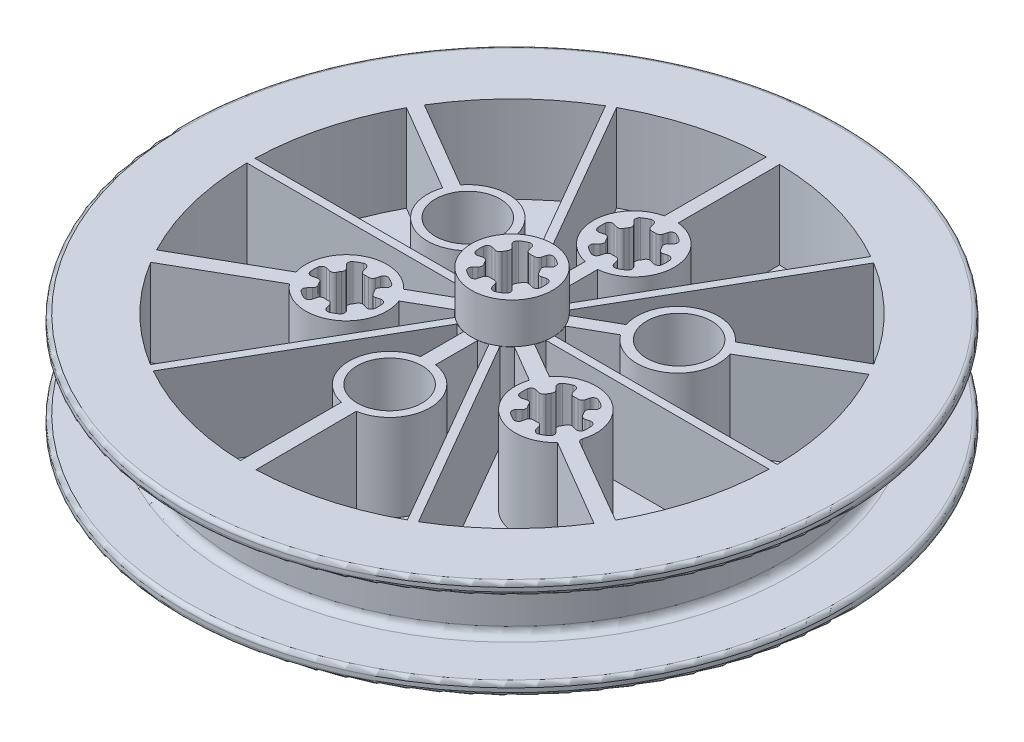
SolidWorks part; units mm, degrees
note: The reader was unsure of these and kept them because the rebuilt part matched: shared geometry of "Sketch1<25>", "Sketch1<26>", "Sketch1<27>".
ref_plane "Front Plane" through (0, 0, 0) normal (0, 0, 1) x (1, 0, 0)
ref_plane "Top Plane" through (0, 0, 0) normal (0, 1, 0) x (1, 0, 0)
ref_plane "Right Plane" through (0, 0, 0) normal (1, 0, 0) x (0, 0, -1)
sketch "Sketch1" plane through (0, 0, 0) normal (0, 1, 0) x (1, 0, 0)
  line L0 (-1.0649, -4.9092) -> (-1.0649, -10.2318)
  line L1 (-0.5943, 17.4024) -> (-0.9826, 18.8513)
  line L2 (0.6997, 17.4024) -> (1.088, 18.8513)
  line L3 (2.4675, 15.6346) -> (3.9164, 16.0228)
  line L4 (-2.3621, 15.6346) -> (-3.811, 16.0228)
  line L5 (-2.3621, 14.3405) -> (-3.811, 13.9523)
  line L6 (0.6997, 12.5728) -> (1.088, 11.1239)
  line L7 (1.8205, 13.2198) -> (2.8811, 12.1591)
  line L8 (14.721, -9.3072) -> (15.7817, -10.3678)
  line L9 (1.8205, 16.7553) -> (2.8811, 17.816)
  line L10 (-1.7151, 16.7553) -> (-2.7757, 17.816)
  line L11 (2.4675, 14.3405) -> (3.9164, 13.9523)
  line L12 (-1.7151, 13.2198) -> (-2.7757, 12.1591)
  line L13 (-0.5943, 12.5728) -> (-0.9826, 11.1239)
  line L14 (15.3681, -8.1865) -> (16.817, -8.5747)
  line L15 (15.3681, -6.8924) -> (16.817, -6.5041)
  line L16 (14.721, -5.7717) -> (15.7817, -4.711)
  line L17 (13.6003, -9.9542) -> (13.9885, -11.4031)
  line L18 (12.3062, -9.9542) -> (11.918, -11.4031)
  line L19 (13.6003, -5.1246) -> (13.9885, -3.6757)
  line L20 (12.3062, -5.1246) -> (11.918, -3.6757)
  line L21 (10.5385, -8.1865) -> (9.0896, -8.5747)
  line L22 (11.1855, -9.3072) -> (10.1248, -10.3678)
  line L23 (10.5385, -6.8924) -> (9.0896, -6.5041)
  line L24 (11.1855, -5.7717) -> (10.1248, -4.711)
  line L25 (-15.4208, -8.0952) -> (-16.8697, -8.4834)
  line L26 (-14.7737, -9.2159) -> (-15.8344, -10.2766)
  line L27 (-13.653, -9.863) -> (-14.0412, -11.3118)
  line L28 (-12.3589, -9.863) -> (-11.9707, -11.3118)
  line L29 (-15.4208, -6.8011) -> (-16.8697, -6.4129)
  line L30 (-14.7737, -5.6804) -> (-15.8344, -4.6197)
  line L31 (-11.2382, -9.2159) -> (-10.1775, -10.2766)
  line L32 (-10.5912, -8.0952) -> (-9.1423, -8.4834)
  line L33 (-12.3589, -5.0333) -> (-11.9707, -3.5844)
  line L34 (-13.653, -5.0333) -> (-14.0412, -3.5844)
  line L35 (-11.2382, -5.6804) -> (-10.1775, -4.6197)
  line L36 (-10.5912, -6.8011) -> (-9.1423, -6.4129)
  line L37 (-1.0649, 19.8908) -> (-1.0649, 19.8682)
  line L38 (0.647, 2.4148) -> (1.0353, 3.8637)
  line L39 (4.6156, 1.9825) -> (8.9512, 4.4452)
  line L40 (1.7678, 1.7678) -> (2.8284, 2.8284)
  line L41 (17.6073, -9.3858) -> (28.4662, -15.6821)
  line L42 (2.4148, 0.647) -> (3.8637, 1.0353)
  line L43 (17.7717, 9.1479) -> (28.5298, 15.5661)
  line L44 (2.4148, -0.647) -> (3.8637, -1.0353)
  line L46 (1.7678, -1.7678) -> (2.8284, -2.8284)
  line L47 (-1.0649, 10.0984) -> (-1.0649, 10.1069)
  line L48 (0.647, -2.4148) -> (1.0353, -3.8637)
  line L49 (16.5972, -10.9733) -> (27.4769, -17.3571)
  line L50 (-0.647, -2.4148) -> (-1.0353, -3.8637)
  line L51 (27.7183, 16.969) -> (16.8151, 10.7758)
  line L52 (-1.7678, -1.7678) -> (-2.8284, -2.8284)
  line L53 (8.2092, 5.8876) -> (3.7427, 3.3506)
  line L54 (-2.4148, -0.647) -> (-3.8637, -1.0353)
  line L56 (-2.4148, 0.647) -> (-3.8637, 1.0353)
  line L57 (0.5558, 4.9925) -> (0.5558, 10.0059)
  line L58 (-1.7678, 1.7678) -> (-2.8284, 2.8284)
  line L59 (0.5558, 19.9686) -> (0.5558, 32.4952)
  line L60 (-0.647, 2.4148) -> (-1.0353, 3.8637)
  line L61 (-1.0649, 32.4826) -> (-1.0649, 19.8908)
  line L63 (-28.5547, 15.5203) -> (-17.7345, 9.1713)
  line L65 (-27.7455, 16.9245) -> (-16.9656, 10.5992)
  line L67 (3.6952, -3.4029) -> (8.1782, -6.0333)
  line L68 (4.6591, -1.8781) -> (9.0388, -4.4175)
  line L69 (0.5558, 32.4952) -> (0.5558, 19.9686)
  line L70 (-1.0649, 32.4826) -> (-1.0649, 19.8908)
  line L71 (0.5558, 10.0206) -> (0.5558, 4.9925)
  line L72 (-1.0649, 10.0984) -> (-1.0649, 4.9092)
  line L75 (0.8161, -20.0501) -> (0.8805, -32.4881)
  line L76 (-1.0649, -20.0024) -> (-1.0649, -32.4826)
  line L77 (0.738, -4.9689) -> (0.738, -10.1719)
  line L78 (27.7183, 16.969) -> (16.8151, 10.7758)
  line L80 (8.2092, 5.8876) -> (3.7427, 3.3506)
  line L81 (-3.956, -3.0959) -> (-8.3451, -5.619)
  line L82 (-4.7946, -1.4987) -> (-9.3141, -4.0659)
  line L83 (-16.932, -10.5555) -> (-27.8141, -16.8114)
  line L84 (-17.8017, -8.8869) -> (-28.7702, -15.1171)
  line L85 (-1.0649, 10.1069) -> (-1.0649, 4.9092)
  line L87 (-16.9656, 10.5992) -> (-27.7455, 16.9245)
  line L88 (-28.5547, 15.5203) -> (-17.7345, 9.1713)
  line L90 (-4.7946, -1.4987) -> (-9.3141, -4.0659)
  line L91 (-17.8017, -8.8869) -> (-28.7702, -15.1171)
  line L92 (-27.8141, -16.8114) -> (-16.932, -10.5555)
  line L93 (-8.3451, -5.619) -> (-3.956, -3.0959)
  line L95 (-1.0649, -20.0024) -> (-1.0649, -32.4826)
  line L96 (0.8805, -32.4881) -> (0.8161, -20.0501)
  line L98 (3.6952, -3.4029) -> (8.1782, -6.0333)
  line L99 (16.5972, -10.9733) -> (27.4769, -17.3571)
  line L100 (17.6073, -9.3858) -> (28.4662, -15.6821)
  line L103 (3.7427, 3.3506) -> (8.2092, 5.8876)
  line L104 (16.8151, 10.7758) -> (27.7183, 16.969)
  line L105 (0.5558, 32.4952) -> (0.5558, 19.9686)
  line L106 (-1.0649, 32.4826) -> (-1.0649, 19.8682)
  line L107 (0.5558, 10.0059) -> (0.5558, 4.9925)
  line L108 (-1.0649, 10.1069) -> (-1.0649, 4.9092)
  line L113 (16.0318, 28.2707) -> (2.2919, 4.4701)
  line L114 (-4.0247, 3.006) -> (-8.5013, 5.3763)
  line L115 (16.8939, 27.7641) -> (3.1319, 3.9275)
  line L116 (32.499, 0.2514) -> (5.0172, 0.2502)
  line L117 (32.4914, -0.7485) -> (4.9673, -0.7485)
  line L118 (16.4672, -28.0193) -> (2.7253, -4.2199)
  line L119 (15.5974, -28.5126) -> (1.8354, -4.6761)
  line L120 (-16.0318, -28.2707) -> (-2.2919, -4.4701)
  line L121 (-16.8939, -27.7641) -> (-3.1319, -3.9275)
  line L122 (-32.499, -0.2514) -> (-5.0172, -0.2502)
  line L123 (-32.4914, 0.7485) -> (-4.9673, 0.7485)
  line L124 (-16.4672, 28.0193) -> (-2.7253, 4.2199)
  line L125 (-15.5974, 28.5126) -> (-1.8354, 4.6761)
  line L126 (28.5298, 15.5661) -> (17.6376, 9.3792) [skipped]
  line L127 (8.9876, 4.4659) -> (4.6156, 1.9825) [skipped]
  line L128 (-1.0649, -4.9092) -> (-1.0649, -10.1069) [skipped]
  line L129 (0.738, -4.9689) -> (0.7642, -10.0314) [skipped]
  line L130 (-4.773, 1.566) -> (-9.4427, 4.0386)
  arc A0 (0.647, 2.4148) -> (-0.647, 2.4148) centre (0, 0) ccw
  arc A1 (-2.8284, -2.8284) -> (-1.0353, -3.8637) centre (0, 0) ccw
  arc A2 (-1.0649, 4.9092) -> (-1.8354, 4.6761) centre (0, 0) ccw
  arc A5 (-1.0649, 32.4826) -> (-15.5974, 28.5126) centre (0, 0) ccw
  arc A7 (-0.9826, 18.8513) -> (-2.7757, 17.816) centre (0.0527, 14.9876) ccw
  arc A8 (-1.7151, 16.7553) -> (-2.3621, 15.6346) centre (0.0527, 14.9876) ccw
  arc A9 (-1.0649, 19.8682) -> (-1.0649, 10.1069) centre (0.0527, 14.9876) ccw
  circle A16 centre (13.0937, 7.5462) radius 4
  arc A18 (11.918, -3.6757) -> (10.1248, -4.711) centre (12.9533, -7.5394) ccw
  arc A19 (17.6073, -9.3858) -> (9.0388, -4.4175) centre (12.9533, -7.5394) ccw
  arc A21 (-14.0412, -3.5844) -> (-15.8344, -4.6197) centre (-13.006, -7.4481) ccw
  arc A22 (-9.3141, -4.0659) -> (-17.8017, -8.8869) centre (-13.006, -7.4481) ccw
  arc A23 (0.6997, 17.4024) -> (-0.5943, 17.4024) centre (0.0527, 14.9876) ccw
  arc A24 (2.4675, 15.6346) -> (1.8205, 16.7553) centre (0.0527, 14.9876) ccw
  arc A25 (1.8205, 13.2198) -> (2.4675, 14.3405) centre (0.0527, 14.9876) ccw
  arc A26 (-0.5943, 12.5728) -> (0.6997, 12.5728) centre (0.0527, 14.9876) ccw
  arc A27 (-2.3621, 14.3405) -> (-1.7151, 13.2198) centre (0.0527, 14.9876) ccw
  arc A28 (14.721, -9.3072) -> (15.3681, -8.1865) centre (12.9533, -7.5394) ccw
  arc A29 (15.3681, -6.8924) -> (14.721, -5.7717) centre (12.9533, -7.5394) ccw
  arc A30 (12.3062, -9.9542) -> (13.6003, -9.9542) centre (12.9533, -7.5394) ccw
  arc A31 (13.6003, -5.1246) -> (12.3062, -5.1246) centre (12.9533, -7.5394) ccw
  arc A32 (11.1855, -5.7717) -> (10.5385, -6.8924) centre (12.9533, -7.5394) ccw
  arc A33 (10.5385, -8.1865) -> (11.1855, -9.3072) centre (12.9533, -7.5394) ccw
  arc A34 (-15.4208, -8.0952) -> (-14.7737, -9.2159) centre (-13.006, -7.4481) ccw
  arc A35 (-13.653, -9.863) -> (-12.3589, -9.863) centre (-13.006, -7.4481) ccw
  arc A36 (-14.7737, -5.6804) -> (-15.4208, -6.8011) centre (-13.006, -7.4481) ccw
  arc A37 (-11.2382, -9.2159) -> (-10.5912, -8.0952) centre (-13.006, -7.4481) ccw
  arc A38 (-10.5912, -6.8011) -> (-11.2382, -5.6804) centre (-13.006, -7.4481) ccw
  arc A39 (-12.3589, -5.0333) -> (-13.653, -5.0333) centre (-13.006, -7.4481) ccw
  circle A40 centre (-13.006, -7.4481) radius 2.5 [skipped]
  circle A41 centre (12.9533, -7.5394) radius 2.5 [skipped]
  arc A42 (-1.7678, 1.7678) -> (-2.4148, 0.647) centre (0, 0) ccw
  arc A43 (-2.4148, -0.647) -> (-1.7678, -1.7678) centre (0, 0) ccw
  arc A44 (-0.647, -2.4148) -> (0.647, -2.4148) centre (0, 0) ccw
  arc A45 (1.7678, -1.7678) -> (2.4148, -0.647) centre (0, 0) ccw
  arc A46 (2.4148, 0.647) -> (1.7678, 1.7678) centre (0, 0) ccw
  arc A48 (0.5558, 10.0059) -> (0.5558, 19.9692) centre (0.0527, 14.9876) ccw
  arc A49 (3.7427, 3.3506) -> (3.1319, 3.9275) centre (0, 0) ccw
  arc A50 (-4.773, 1.566) -> (-4.9673, 0.7485) centre (0, 0) ccw
  arc A51 (4.6591, -1.8781) -> (4.9673, -0.7485) centre (0, 0) ccw
  arc A52 (0.738, -4.9689) -> (1.8354, -4.6761) centre (0, 0) ccw
  arc A53 (-3.956, -3.0959) -> (-3.1319, -3.9275) centre (0, 0) ccw
  arc A54 (1.0353, -3.8637) -> (2.8284, -2.8284) centre (0, 0) ccw
  arc A55 (3.8637, -1.0353) -> (3.8637, 1.0353) centre (0, 0) ccw
  arc A56 (2.8284, 2.8284) -> (1.0353, 3.8637) centre (0, 0) ccw
  arc A57 (-1.0353, 3.8637) -> (-2.8284, 2.8284) centre (0, 0) ccw
  arc A58 (-3.8637, 1.0353) -> (-3.8637, -1.0353) centre (0, 0) ccw
  arc A59 (15.7817, -4.711) -> (13.9885, -3.6757) centre (12.9533, -7.5394) ccw
  arc A60 (16.817, -8.5747) -> (16.817, -6.5041) centre (12.9533, -7.5394) ccw
  arc A61 (13.9885, -11.4031) -> (15.7817, -10.3678) centre (12.9533, -7.5394) ccw
  arc A62 (10.1248, -10.3678) -> (11.918, -11.4031) centre (12.9533, -7.5394) ccw
  arc A63 (9.0896, -6.5041) -> (9.0896, -8.5747) centre (12.9533, -7.5394) ccw
  arc A64 (-10.1775, -4.6197) -> (-11.9707, -3.5844) centre (-13.006, -7.4481) ccw
  arc A65 (-9.1423, -8.4834) -> (-9.1423, -6.4129) centre (-13.006, -7.4481) ccw
  arc A66 (-11.9707, -11.3118) -> (-10.1775, -10.2766) centre (-13.006, -7.4481) ccw
  arc A67 (-15.8344, -10.2766) -> (-14.0412, -11.3118) centre (-13.006, -7.4481) ccw
  arc A68 (-16.8697, -6.4129) -> (-16.8697, -8.4834) centre (-13.006, -7.4481) ccw
  arc A69 (2.8811, 17.816) -> (1.088, 18.8513) centre (0.0527, 14.9876) ccw
  arc A70 (3.9164, 13.9523) -> (3.9164, 16.0228) centre (0.0527, 14.9876) ccw
  arc A71 (1.088, 11.1239) -> (2.8811, 12.1591) centre (0.0527, 14.9876) ccw
  arc A72 (-2.7757, 12.1591) -> (-0.9826, 11.1239) centre (0.0527, 14.9876) ccw
  arc A73 (-3.811, 16.0228) -> (-3.811, 13.9523) centre (0.0527, 14.9876) ccw
  arc A75 (8.1782, -6.0333) -> (16.5972, -10.9733) centre (12.9533, -7.5394) ccw
  arc A77 (-16.932, -10.5555) -> (-8.3451, -5.619) centre (-13.006, -7.4481) ccw
  arc A78 (27.7183, 16.969) -> (16.8939, 27.7641) centre (0, 0) ccw
  arc A79 (-28.5547, 15.5203) -> (-32.4914, 0.7485) centre (0, 0) ccw
  arc A80 (-27.8141, -16.8114) -> (-16.8939, -27.7641) centre (0, 0) ccw
  arc A81 (0.8805, -32.4881) -> (15.5974, -28.5126) centre (0, 0) ccw
  arc A82 (28.4662, -15.6821) -> (32.4914, -0.7485) centre (0, 0) ccw
  arc A83 (-1.0649, 32.4826) -> (-15.5974, 28.5126) centre (0, 0) ccw
  arc A84 (27.7183, 16.969) -> (16.8939, 27.7641) centre (0, 0) ccw
  arc A85 (28.4662, -15.6821) -> (32.4914, -0.7485) centre (0, 0) ccw
  arc A86 (0.8805, -32.4881) -> (15.5974, -28.5126) centre (0, 0) ccw
  arc A87 (-27.8141, -16.8114) -> (-16.8939, -27.7641) centre (0, 0) ccw
  arc A88 (-28.5547, 15.5203) -> (-32.4914, 0.7485) centre (0, 0) ccw
  arc A89 (27.7183, 16.969) -> (16.8939, 27.7641) centre (0, 0) ccw
  arc A90 (0.5558, 19.9692) -> (0.5558, 10.0206) centre (0.0534, 14.9949) cw
  arc A91 (8.9512, 4.4452) -> (17.7717, 9.1479) centre (13.0144, 7.4476) ccw
  arc A92 (3.7427, 3.3506) -> (3.1319, 3.9275) centre (0, 0) ccw
  arc A93 (27.7183, 16.969) -> (16.8939, 27.7641) centre (0, 0) ccw
  arc A94 (-1.0649, 32.4826) -> (-15.5974, 28.5126) centre (0, 0) ccw
  arc A95 (-1.0649, 19.8908) -> (-1.0649, 10.1069) centre (0.0553, 14.9989) ccw
  circle A96 centre (-13.006, 7.5462) radius 4
  arc A97 (-17.7345, 9.1713) -> (-9.4427, 4.0386) centre (-13.006, 7.5462) ccw
  arc A98 (-1.0649, 4.9092) -> (-1.8354, 4.6761) centre (0, 0) ccw
  arc A99 (-4.773, 1.566) -> (-4.9673, 0.7485) centre (0, 0) ccw
  arc A100 (-28.5547, 15.5203) -> (-32.4914, 0.7485) centre (0, 0) ccw
  arc A101 (-9.3141, -4.0659) -> (-17.8017, -8.8869) centre (-13.006, -7.4481) ccw
  arc A102 (-28.5547, 15.5203) -> (-32.4914, 0.7485) centre (0, 0) ccw
  arc A103 (-27.8141, -16.8114) -> (-16.8939, -27.7641) centre (0, 0) ccw
  arc A104 (0.8805, -32.4881) -> (15.5974, -28.5126) centre (0, 0) ccw
  arc A105 (28.5298, 15.5661) -> (32.499, 0.2514) centre (0, 0) cw
  arc A106 (0.5558, 32.4952) -> (16.0318, 28.2707) centre (0, 0) cw
  arc A107 (-1.0649, 32.4826) -> (-15.5974, 28.5126) centre (0, 0) ccw
  arc A108 (3.7427, 3.3506) -> (3.1319, 3.9275) centre (0, 0) ccw
  circle A109 centre (0, 0) radius 4
  arc A110 (-1.0649, 19.8682) -> (-1.0649, 10.1069) centre (0.0527, 14.9876) ccw
  arc A113 (8.1782, -6.0333) -> (16.5972, -10.9733) centre (12.9533, -7.5394) ccw
  arc A115 (-9.3141, -4.0659) -> (-17.8017, -8.8869) centre (-13.006, -7.4481) ccw
  arc A117 (4.6591, -1.8781) -> (4.9673, -0.7485) centre (0, 0) ccw
  arc A118 (0.738, -4.9689) -> (1.8354, -4.6761) centre (0, 0) ccw
  arc A119 (-1.0649, 4.9092) -> (-1.8354, 4.6761) centre (0, 0) ccw
  arc A120 (-4.773, 1.566) -> (-4.9673, 0.7485) centre (0, 0) ccw
  arc A121 (-3.956, -3.0959) -> (-3.1319, -3.9275) centre (0, 0) ccw
  arc A122 (-16.932, -10.5555) -> (-8.3451, -5.619) centre (-13.006, -7.4481) ccw
  circle A123 centre (0, -15.1171) radius 4
  arc A124 (17.6073, -9.3858) -> (9.0388, -4.4175) centre (12.9533, -7.5394) ccw
  arc A125 (0.5558, 10.0059) -> (0.5558, 19.9692) centre (0.0527, 14.9876) ccw
  arc A126 (-8.5013, 5.3763) -> (-16.9656, 10.5992) centre (-13.006, 7.5462) ccw
  arc A127 (-16.4672, 28.0193) -> (-27.7455, 16.9245) centre (0, 0) ccw
  arc A128 (2.2919, 4.4701) -> (0.5558, 4.9925) centre (0, 0) ccw
  arc A129 (2.2919, 4.4701) -> (0.5558, 4.9925) centre (0, 0) ccw
  arc A130 (2.2919, 4.4701) -> (0.5558, 4.9925) centre (0, 0) ccw
  arc A131 (-2.7253, 4.2199) -> (-4.0247, 3.006) centre (0, 0) ccw
  arc A132 (-2.7253, 4.2199) -> (-4.0247, 3.006) centre (0, 0) ccw
  arc A133 (-2.7253, 4.2199) -> (-4.0247, 3.006) centre (0, 0) ccw
  arc A134 (2.7253, -4.2199) -> (3.6952, -3.4029) centre (0, 0) ccw
  arc A135 (2.7253, -4.2199) -> (3.6952, -3.4029) centre (0, 0) ccw
  arc A136 (5.0172, 0.2502) -> (4.6156, 1.9825) centre (0, 0) ccw
  arc A137 (5.0172, 0.2502) -> (4.6156, 1.9825) centre (0, 0) ccw
  arc A138 (-5.0172, -0.2502) -> (-4.7946, -1.4987) centre (0, 0) ccw
  arc A139 (-5.0172, -0.2502) -> (-4.7946, -1.4987) centre (0, 0) ccw
  arc A140 (-5.0172, -0.2502) -> (-4.7946, -1.4987) centre (0, 0) ccw
  arc A141 (-2.2919, -4.4701) -> (-1.0649, -4.9092) centre (0, 0) ccw
  arc A142 (-2.2919, -4.4701) -> (-1.0649, -4.9092) centre (0, 0) ccw
  circle A143 centre (0, 0) radius 40.7
  arc A144 (-16.4672, 28.0193) -> (-27.7455, 16.9245) centre (0, 0) ccw
  arc A145 (-16.4672, 28.0193) -> (-27.7455, 16.9245) centre (0, 0) ccw
  arc A146 (-16.4672, 28.0193) -> (-27.7455, 16.9245) centre (0, 0) ccw
  arc A147 (-16.4672, 28.0193) -> (-27.7455, 16.9245) centre (0, 0) ccw
  arc A148 (-1.0649, 32.4826) -> (-15.5974, 28.5126) centre (0, 0) ccw
  arc A149 (16.0318, 28.2707) -> (0.5558, 32.4952) centre (0, 0) ccw
  arc A150 (16.0318, 28.2707) -> (0.5558, 32.4952) centre (0, 0) ccw
  arc A151 (16.0318, 28.2707) -> (0.5558, 32.4952) centre (0, 0) ccw
  arc A152 (16.0318, 28.2707) -> (0.5558, 32.4952) centre (0, 0) ccw
  arc A153 (16.0318, 28.2707) -> (0.5558, 32.4952) centre (0, 0) ccw
  arc A154 (16.8939, 27.7641) -> (27.7183, 16.969) centre (0, 0) cw
  arc A155 (32.499, 0.2514) -> (28.5298, 15.5661) centre (0, 0) ccw
  arc A156 (32.499, 0.2514) -> (28.5298, 15.5661) centre (0, 0) ccw
  arc A157 (32.4914, -0.7485) -> (28.4662, -15.6821) centre (0, 0) cw
  arc A158 (32.499, 0.2514) -> (28.5298, 15.5661) centre (0, 0) ccw
  arc A159 (28.4662, -15.6821) -> (32.4914, -0.7485) centre (0, 0) ccw
  arc A160 (16.4672, -28.0193) -> (27.4769, -17.3571) centre (0, 0) ccw
  arc A161 (16.4672, -28.0193) -> (27.4769, -17.3571) centre (0, 0) ccw
  arc A162 (16.4672, -28.0193) -> (27.4424, -17.4116) centre (0, 0) ccw
  arc A163 (16.4672, -28.0193) -> (27.4769, -17.3571) centre (0, 0) ccw
  arc A164 (0.8805, -32.4881) -> (15.5974, -28.5126) centre (0, 0) ccw
  arc A165 (-16.0318, -28.2707) -> (-1.0649, -32.4826) centre (0, 0) ccw
  arc A166 (-16.0318, -28.2707) -> (-1.0649, -32.4826) centre (0, 0) ccw
  arc A167 (-16.0318, -28.2707) -> (-1.0649, -32.4826) centre (0, 0) ccw
  arc A168 (-16.0318, -28.2707) -> (-1.0649, -32.4826) centre (0, 0) ccw
  arc A169 (-27.8141, -16.8114) -> (-16.8939, -27.7641) centre (0, 0) ccw
  arc A170 (-32.499, -0.2514) -> (-28.7702, -15.1171) centre (0, 0) ccw
  arc A171 (-32.499, -0.2514) -> (-28.7702, -15.1171) centre (0, 0) ccw
  arc A172 (-32.499, -0.2514) -> (-28.7702, -15.1171) centre (0, 0) ccw
  arc A173 (-32.499, -0.2514) -> (-28.7702, -15.1171) centre (0, 0) ccw
  arc A174 (-32.499, -0.2514) -> (-28.7702, -15.1171) centre (0, 0) ccw
  arc A175 (-28.5547, 15.5203) -> (-32.4914, 0.7485) centre (0, 0) ccw
  arc A176 (27.7183, 16.969) -> (16.8939, 27.7641) centre (0, 0) ccw
  circle A177 centre (0, 0) radius 32.5
  circle A178 centre (0, 0) radius 33.5
  arc A180 (16.8151, 10.7758) -> (8.2092, 5.8876) centre (13.0144, 7.4476) ccw
  arc A181 (0.8161, -20.0501) -> (0.738, -10.1719) centre (0, -15.1171) ccw
  arc A182 (-1.0649, -10.2318) -> (-1.0649, -20.0024) centre (0, -15.1171) ccw
  point P26 (0.0683, 0.0439)
  point P35 (0, 0)
  point P107 (0, 0)
  point P184 (0, 0)
  point P201 (0, 0)
  point P227 (0, 0)
  dimension "D1" = 3
  dimension "D2" = 2
  dimension "D3" = 67
  dimension "D4" = 10
  dimension "D5" = 3
  dimension "D6" = 32.5
  dimension "D7" = 81.4
  dimension "D8" = 8
  dimension "D9" = 5
  dimension "D10" = 6
extrude "Boss-Extrude2" add sketch "Sketch1" along normal blind 12.25
sketch "Sketch5" plane through (0, 12.25, 0) normal (0, 1, 0) x (1, 0, 0)
  line L0 (0.647, 2.4148) -> (1.0353, 3.8637)
  line L1 (-1.0353, 3.8637) -> (-0.647, 2.4148)
  line L2 (-2.8284, 2.8284) -> (-1.7678, 1.7678)
  line L3 (-3.8637, 1.0353) -> (-2.4148, 0.647)
  line L4 (-3.8637, -1.0353) -> (-2.4148, -0.647)
  line L5 (-2.8284, -2.8284) -> (-1.7678, -1.7678)
  line L6 (-0.647, -2.4148) -> (-1.0353, -3.8637)
  line L7 (0.647, -2.4148) -> (1.0353, -3.8637)
  line L8 (0.647, -2.4148) -> (1.0353, -3.8637) construction
  line L9 (1.7678, 1.7678) -> (2.8284, 2.8284)
  line L10 (1.7678, 1.7678) -> (2.8284, 2.8284) construction
  line L11 (2.4148, 0.647) -> (3.8637, 1.0353)
  line L12 (2.4148, -0.647) -> (3.8637, -1.0353)
  line L13 (1.7678, -1.7678) -> (2.8284, -2.8284)
  line L14 (1.7678, -1.7678) -> (2.8284, -2.8284) construction
  circle A0 centre (0, 0) radius 5
  arc A1 (-1.0353, 3.8637) -> (-2.8284, 2.8284) centre (0, 0) ccw
  arc A2 (-1.7678, 1.7678) -> (-2.4148, 0.647) centre (0, 0) ccw
  arc A3 (0.647, 2.4148) -> (-0.647, 2.4148) centre (0, 0) ccw
  arc A4 (-3.8637, 1.0353) -> (-3.8637, -1.0353) centre (0, 0) ccw
  arc A5 (-2.8284, -2.8284) -> (-1.0353, -3.8637) centre (0, 0) ccw
  arc A6 (1.0353, -3.8637) -> (2.8284, -2.8284) centre (0, 0) ccw
  arc A7 (3.8637, -1.0353) -> (3.8637, 1.0353) centre (0, 0) ccw
  arc A8 (2.8284, 2.8284) -> (1.0353, 3.8637) centre (0, 0) ccw
  arc A9 (-2.4148, -0.647) -> (-1.7678, -1.7678) centre (0, 0) ccw
  arc A10 (1.7678, -1.7678) -> (2.4148, -0.647) centre (0, 0) ccw
  arc A11 (2.4148, 0.647) -> (1.7678, 1.7678) centre (0, 0) ccw
  arc A12 (-0.647, -2.4148) -> (0.647, -2.4148) centre (0, 0) ccw
extrude "Boss-Extrude20" add sketch "Sketch5" along normal blind 5
extrude "Boss-Extrude25" add sketch "Sketch1<25>" along normal blind 1.9 contours A143 A177 A81 A165 A80 A170 A79 A127 A5 A106 A78 A105 A82 A161 A160
sketch "Sketch1<25>" plane through (0, 0, 0) normal (0, 1, 0) x (1, 0, 0) same geometry as "Sketch1"
extrude "Boss-Extrude26" add sketch "Sketch1<26>" along normal blind 12.25 contours A178 A177 A81 A165 A80 A170 A79 A127 A5 A106 A78 A105 A82 A161 A160
sketch "Sketch1<26>" plane through (0, 0, 0) normal (0, 1, 0) x (1, 0, 0) same geometry as "Sketch1"
extrude "Boss-Extrude27" add sketch "Sketch1<27>" along normal blind 1.5 contours A143 A178
sketch "Sketch1<27>" plane through (0, 0, 0) normal (0, 1, 0) x (1, 0, 0) same geometry as "Sketch1"
sketch "Sketch7" plane through (0, 0, 0) normal (0, -1, 0) x (1, 0, 0)
  circle A0 centre (0, 0) radius 32.5
  circle A1 centre (0, 0) radius 33
  dimension "D1" = 65
  dimension "D2" = 66
extrude "Boss-Extrude31" add sketch "Sketch7" along normal blind 0.5
fillet "Fillet1" radius 0.2 2 edges at (0, -0.5, -32.5) (0, -0.5, -33)
sketch "Sketch8" plane through (0, 12.25, 0) normal (0, 1, 0) x (1, 0, 0)
  circle A0 centre (0, 0) radius 40.7
  circle A1 centre (0, 0) radius 32.5
  dimension "D1" = 65
extrude "Boss-Extrude32" add sketch "Sketch8" against normal blind 1.5 separate body
sketch "Sketch11" plane through (0, 0, 0) normal (0, -1, 0) x (1, 0, 0)
  line L0 (-16.0318, 28.2707) -> (-2.2919, 4.4701)
  line L1 (-16.8939, 27.7641) -> (-3.1319, 3.9275)
  line L2 (16.4672, 28.0193) -> (2.7253, 4.2199)
  line L3 (15.5974, 28.5126) -> (1.8354, 4.6761)
  line L4 (32.499, -0.2514) -> (5.0172, -0.2502)
  line L5 (32.4914, 0.7485) -> (4.9673, 0.7485)
  line L6 (16.0318, -28.2707) -> (2.2919, -4.4701)
  line L7 (16.8939, -27.7641) -> (3.1319, -3.9275)
  line L9 (-2.7253, -4.2199) -> (-15.9203, -27.0721)
  line L10 (-32.499, 0.2514) -> (-5.0172, 0.2502)
  line L11 (-32.4914, -0.7485) -> (-4.9673, -0.7485)
  line L12 (-1.0649, 20.0024) -> (-1.0649, 32.4826) construction
  line L13 (-1.0649, 32.4826) -> (-1.0649, 20.0024)
  line L14 (0.8805, 32.4881) -> (0.8161, 20.0501)
  line L15 (-1.0649, 10.2318) -> (-1.0649, 4.9092)
  line L16 (0.738, 10.1719) -> (0.738, 4.9689)
  line L17 (3.6952, 3.4029) -> (8.1782, 6.0333)
  line L18 (4.6591, 1.8781) -> (9.0388, 4.4175)
  line L19 (-3.956, 3.0959) -> (-8.3451, 5.619)
  line L20 (-4.7946, 1.4987) -> (-9.3141, 4.0659)
  line L23 (-1.0649, -4.9092) -> (-1.0649, -10.1069)
  line L24 (0.5558, -4.9925) -> (0.5558, -10.0207)
  line L25 (4.6156, -1.9825) -> (9.1697, -4.5693)
  line L26 (3.7427, -3.3506) -> (8.4157, -6.0048)
  line L27 (27.7183, -16.969) -> (16.8151, -10.7758) construction
  line L28 (-16.932, 10.5555) -> (-27.8141, 16.8114)
  line L29 (-17.8017, 8.8869) -> (-28.7702, 15.1171)
  line L30 (16.5972, 10.9733) -> (27.4769, 17.3571)
  line L31 (17.6073, 9.3858) -> (28.4662, 15.6821)
  line L32 (17.6602, -9.392) -> (28.5298, -15.5661)
  line L33 (16.8134, -10.7748) -> (27.7183, -16.969)
  line L34 (-17.7345, -9.1713) -> (-28.5547, -15.5203)
  line L35 (-16.9656, -10.5992) -> (-27.7455, -16.9245)
  line L36 (-1.0649, -19.8531) -> (-1.0649, -32.4826)
  line L37 (0.5558, -19.9544) -> (0.5558, -32.4952)
  line L38 (-4.773, -1.566) -> (-9.4427, -4.0386)
  line L39 (-4.0247, -3.006) -> (-8.5013, -5.3763)
  line L40 (-1.0649, -10.1069) -> (-1.0649, -10.122)
  line L41 (-16.4672, -28.0193) -> (-2.7253, -4.2199) construction
  line L42 (-16.4672, -28.0193) -> (-2.7253, -4.2199)
  line L43 (-15.5974, -28.5126) -> (-1.8354, -4.6761)
  line L44 (-1.8354, -4.6761) -> (-15.1653, -27.7641)
  line L45 (-15.5974, -28.5126) -> (-1.8354, -4.6761) construction
  line L46 (-15.1653, -27.7641) -> (-15.5747, -28.4732)
  line L47 (-15.9203, -27.0721) -> (-16.4672, -28.0193)
  circle A0 centre (0, 0) radius 32.5 construction
  circle A1 centre (0, 15.1171) radius 5 construction
  arc A2 (-1.0649, 20.0024) -> (-1.0649, 10.2318) centre (0, 15.1171) ccw
  arc A8 (0.738, 10.1719) -> (0.8161, 20.0501) centre (0, 15.1171) ccw
  arc A9 (-8.3451, 5.619) -> (-16.932, 10.5555) centre (-13.006, 7.4481) ccw
  arc A10 (-1.0649, 20.0024) -> (-1.0649, 10.2318) centre (0, 15.1171) ccw
  arc A11 (16.5972, 10.9733) -> (8.1782, 6.0333) centre (12.9533, 7.5394) ccw
  arc A12 (17.6602, -9.392) -> (9.1697, -4.5693) centre (13.0937, -7.5462) ccw
  arc A13 (0.5558, -19.9544) -> (0.5558, -10.0207) centre (0.0527, -14.9876) ccw
  arc A14 (-1.0649, 4.9092) -> (-2.2919, 4.4701) centre (0, 0) ccw
  arc A15 (-9.4427, -4.0386) -> (-17.7345, -9.1713) centre (-13.006, -7.5462) ccw
  arc A16 (0.738, 10.1719) -> (0.8161, 20.0501) centre (0, 15.1171) ccw
  arc A17 (9.0388, 4.4175) -> (17.6073, 9.3858) centre (12.9533, 7.5394) ccw
  arc A18 (-17.8017, 8.8869) -> (-9.3141, 4.0659) centre (-13.006, 7.4481) ccw
  arc A19 (-3.1319, 3.9275) -> (-3.956, 3.0959) centre (0, 0) ccw
  arc A20 (-4.7946, 1.4987) -> (-5.0172, 0.2502) centre (0, 0) ccw
  arc A21 (-4.9673, -0.7485) -> (-4.773, -1.566) centre (0, 0) ccw
  arc A22 (3.6952, 3.4029) -> (0.738, 4.9689) centre (0, 0) ccw
  arc A23 (4.9673, 0.7485) -> (4.6591, 1.8781) centre (0, 0) ccw
  arc A24 (4.6156, -1.9825) -> (5.0172, -0.2502) centre (0, 0) ccw
  arc A25 (3.1319, -3.9275) -> (3.7427, -3.3506) centre (0, 0) ccw
  arc A26 (0.5558, -4.9925) -> (2.2919, -4.4701) centre (0, 0) ccw
  arc A27 (-4.0247, -3.006) -> (-2.7253, -4.2199) centre (0, 0) ccw
  arc A28 (8.4157, -6.0048) -> (16.8134, -10.7748) centre (13.0937, -7.5462) ccw
  arc A29 (-16.9656, -10.5992) -> (-8.4093, -5.5787) centre (-13.006, -7.5462) ccw
  circle A31 centre (0, 0) radius 32.5
  arc A33 (16.8939, -27.7641) -> (27.7183, -16.969) centre (0, 0) ccw
  arc A34 (28.5298, -15.5661) -> (32.499, -0.2514) centre (0, 0) ccw
  arc A35 (32.4914, 0.7485) -> (28.4662, 15.6821) centre (0, 0) ccw
  arc A36 (27.4769, 17.3571) -> (16.4672, 28.0193) centre (0, 0) ccw
  arc A37 (15.5974, 28.5126) -> (0.8805, 32.4881) centre (0, 0) ccw
  arc A38 (-1.0649, 32.4826) -> (-16.0318, 28.2707) centre (0, 0) ccw
  arc A39 (-16.8939, 27.7641) -> (-27.8141, 16.8114) centre (0, 0) ccw
  arc A40 (-28.7702, 15.1171) -> (-32.499, 0.2514) centre (0, 0) ccw
  arc A41 (-32.4914, -0.7485) -> (-28.5547, -15.5203) centre (0, 0) ccw
  arc A42 (0.5558, -19.9544) -> (0.5558, -10.0207) centre (0.0527, -14.9876) ccw
  arc A43 (0.5558, -19.9544) -> (0.5558, -10.0207) centre (0.0527, -14.9876) ccw
  arc A44 (0.5558, -19.9544) -> (0.5558, -10.0207) centre (0.0527, -14.9876) ccw
  arc A45 (-1.8354, -4.6761) -> (-1.0649, -4.9092) centre (0, 0) ccw
  arc A46 (-8.5013, -5.3763) -> (-8.4093, -5.5787) centre (-13.006, -7.5462) cw
  arc A47 (-1.0649, -10.122) -> (-1.0649, -19.8531) centre (0.0527, -14.9876) ccw
  circle A48 centre (-13.006, 7.4481) radius 5.007
  circle A49 centre (0, 15.1171) radius 5
  circle A50 centre (12.9533, 7.5394) radius 5.007
  circle A51 centre (13.0937, -7.5462) radius 4.9254
  circle A52 centre (0.0527, -14.9876) radius 4.9923
  circle A53 centre (-13.006, -7.5462) radius 5
  circle A54 centre (0, 0) radius 5.0234
  arc A55 (27.7183, -16.969) -> (28.5298, -15.5661) centre (0, 0) ccw
  point P31 (0, 0)
  point P91 (0, 0)
  point P105 (0, 0)
sketch "Sketch12" plane through (0, 0, 0) normal (0, -1, 0) x (1, 0, 0)
  line L0 (-1.7678, 1.7678) -> (-2.8284, 2.8284)
  line L1 (-1.0353, 3.8637) -> (-0.647, 2.4148)
  line L2 (3.8637, 1.0353) -> (2.4148, 0.647)
  line L3 (10.5385, 8.1865) -> (9.0896, 8.5747)
  line L4 (0.647, 2.4148) -> (1.0353, 3.8637)
  line L5 (10.5385, 6.8924) -> (9.0896, 6.5041)
  line L6 (1.7678, 1.7678) -> (2.8284, 2.8284)
  line L7 (11.1855, 5.7717) -> (10.1248, 4.711)
  line L8 (12.3062, 5.1246) -> (11.918, 3.6757)
  line L9 (2.4148, -0.647) -> (3.8637, -1.0353)
  line L10 (13.6003, 5.1246) -> (13.9885, 3.6757)
  line L11 (1.7678, -1.7678) -> (2.8284, -2.8284)
  line L12 (13.6003, 5.1246) -> (13.9885, 3.6757) construction
  line L13 (0.647, -2.4148) -> (1.0353, -3.8637)
  line L14 (-0.647, -2.4148) -> (-1.0353, -3.8637)
  line L15 (14.721, 5.7717) -> (15.7817, 4.711)
  line L16 (-1.7678, -1.7678) -> (-2.8284, -2.8284)
  line L17 (15.3681, 6.8924) -> (16.817, 6.5041)
  line L18 (-2.4148, -0.647) -> (-3.8637, -1.0353)
  line L19 (3.9164, -16.0228) -> (2.4675, -15.6346)
  line L20 (-2.4148, 0.647) -> (-3.8637, 1.0353)
  line L21 (16.817, 8.5747) -> (15.3681, 8.1865)
  line L22 (-1.7678, 1.7678) -> (-2.8284, 2.8284)
  line L23 (15.3681, 8.1865) -> (16.817, 8.5747) construction
  line L24 (15.7817, 10.3678) -> (14.721, 9.3072)
  line L25 (13.9885, 11.4031) -> (13.6003, 9.9542)
  line L26 (13.6003, 9.9542) -> (13.9885, 11.4031) construction
  line L27 (11.918, 11.4031) -> (12.3062, 9.9542)
  line L28 (12.3062, 9.9542) -> (11.918, 11.4031) construction
  line L29 (10.1248, 10.3678) -> (11.1855, 9.3072)
  line L30 (2.8811, -17.816) -> (1.8205, -16.7553)
  line L31 (1.088, -18.8513) -> (0.6997, -17.4024)
  line L32 (-0.9826, -18.8513) -> (-0.5943, -17.4024)
  line L33 (-1.7151, -16.7553) -> (-2.7757, -17.816)
  line L34 (-2.3621, -15.6346) -> (-3.811, -16.0228)
  line L35 (-2.3621, -14.3405) -> (-3.811, -13.9523)
  line L36 (-1.7151, -13.2198) -> (-2.7757, -12.1591)
  line L37 (-0.5943, -12.5728) -> (-0.9826, -11.1239)
  line L38 (0.6997, -12.5728) -> (1.088, -11.1239)
  line L39 (1.8205, -13.2198) -> (2.8811, -12.1591)
  line L40 (3.9164, -13.9523) -> (2.4675, -14.3405)
  line L41 (-15.8344, 4.6197) -> (-14.7737, 5.6804)
  line L42 (-16.8697, 6.4129) -> (-15.4208, 6.8011)
  line L43 (-16.8697, 8.4834) -> (-15.4208, 8.0952)
  line L44 (-15.8344, 10.2766) -> (-14.7737, 9.2159)
  line L45 (-13.653, 9.863) -> (-14.0412, 11.3118)
  line L46 (-12.3589, 9.863) -> (-11.9707, 11.3118)
  line L47 (-11.2382, 9.2159) -> (-10.1775, 10.2766)
  line L48 (-10.5912, 8.0952) -> (-9.1423, 8.4834)
  line L49 (-10.5912, 6.8011) -> (-9.1423, 6.4129)
  line L50 (-11.2382, 5.6804) -> (-10.1775, 4.6197)
  line L51 (-12.3589, 5.0333) -> (-11.9707, 3.5844)
  line L52 (-14.0412, 3.5844) -> (-13.653, 5.0333)
  line L53 (1.088, -11.1239) -> (0.6997, -12.5728)
  line L54 (-0.9826, -11.1239) -> (-0.5943, -12.5728)
  line L55 (-2.7757, -12.1591) -> (-1.7151, -13.2198)
  circle A0 centre (0, 0) radius 5
  circle A1 centre (0, 0) radius 4
  circle A2 centre (-13.006, 7.4481) radius 4
  circle A3 centre (-13.006, 7.4481) radius 5
  circle A4 centre (0, 15.1171) radius 2.5
  circle A5 centre (0, 15.1171) radius 5
  circle A6 centre (12.9533, 7.5394) radius 4
  circle A7 centre (12.9533, 7.5394) radius 5
  circle A8 centre (13.0937, -7.5462) radius 4
  circle A9 centre (13.0937, -7.5462) radius 5
  circle A10 centre (0.0527, -14.9876) radius 5
  circle A11 centre (0.0527, -14.9876) radius 4
  circle A12 centre (-13.006, -7.5462) radius 5
  circle A13 centre (-13.006, -7.5462) radius 4
  arc A14 (-14.7737, 9.2159) -> (-15.4208, 8.0952) centre (-13.006, 7.4481) ccw
  arc A15 (1.7678, -1.7678) -> (2.4148, -0.647) centre (0, 0) ccw
  arc A16 (11.1855, 9.3072) -> (10.5385, 8.1865) centre (12.9533, 7.5394) ccw
  circle A17 centre (13.0937, -7.5462) radius 2.5
  circle A18 centre (0, 15.1171) radius 4
  arc A19 (0.6997, -12.5728) -> (-0.5943, -12.5728) centre (0.0527, -14.9876) ccw
  arc A20 (-0.3255, -2.4787) -> (-0.647, -2.4148) centre (-0.8693, -4.374) ccw
  arc A21 (-0.647, -2.4148) -> (0.647, -2.4148) centre (0, 0) ccw
  arc A22 (-2.4148, -0.647) -> (-1.7678, -1.7678) centre (0, 0) ccw
  arc A23 (-1.7678, 1.7678) -> (-2.4148, 0.647) centre (0, 0) ccw
  arc A24 (-0.647, 2.4148) -> (0.647, 2.4148) centre (0, 0) cw
  arc A25 (13.6003, 9.9542) -> (12.3062, 9.9542) centre (12.9533, 7.5394) ccw
  arc A26 (15.3681, 8.1865) -> (14.721, 9.3072) centre (12.9533, 7.5394) ccw
  arc A27 (10.5385, 6.8924) -> (11.1855, 5.7717) centre (12.9533, 7.5394) ccw
  arc A28 (12.3062, 5.1246) -> (13.6003, 5.1246) centre (12.9533, 7.5394) ccw
  arc A29 (14.721, 5.7717) -> (15.3681, 6.8924) centre (12.9533, 7.5394) ccw
  arc A30 (1.7678, 1.7678) -> (2.4148, 0.647) centre (0, 0) cw
  arc A31 (-12.3589, 9.863) -> (-13.653, 9.863) centre (-13.006, 7.4481) ccw
  arc A32 (-15.4208, 6.8011) -> (-14.7737, 5.6804) centre (-13.006, 7.4481) ccw
  arc A33 (-13.653, 5.0333) -> (-12.3589, 5.0333) centre (-13.006, 7.4481) ccw
  arc A34 (-11.2382, 5.6804) -> (-10.5912, 6.8011) centre (-13.006, 7.4481) ccw
  arc A35 (-10.5912, 8.0952) -> (-11.2382, 9.2159) centre (-13.006, 7.4481) ccw
  arc A36 (-1.7151, -13.2198) -> (-2.3621, -14.3405) centre (0.0527, -14.9876) ccw
  arc A37 (-2.3621, -15.6346) -> (-1.7151, -16.7553) centre (0.0527, -14.9876) ccw
  arc A38 (-0.5943, -17.4024) -> (0.6997, -17.4024) centre (0.0527, -14.9876) ccw
  arc A39 (1.8205, -16.7553) -> (2.4675, -15.6346) centre (0.0527, -14.9876) ccw
  arc A40 (2.4675, -14.3405) -> (1.8205, -13.2198) centre (0.0527, -14.9876) ccw
  point P189 (0, 0)
  dimension "D1" = 3
extrude "Boss-Extrude34" add sketch "Sketch11" against normal blind 1.5
extrude "Cut-Extrude4" cut sketch "Sketch12" against normal blind 1 contours A3 A2 | A31 L46 A2 L45 | A14 L44 A2 L43 | A32 L42 A2 L41 | A33 L52 A2 L51 | A34 L50 A2 L49 | A35 L48 A2 L47 | A5 A18 | A0 A1 | L1 A24 L4 A1 | A23 L0 A1 L20 | A22 L18 A1 L16 | A15 L11 A1 L9 | L6 A30 L2 A1 | A21 L14 A1 L13 | A7 A6 | A27 L5 A6 L7 | A16 L29 A6 L3 | A25 L25 A6 L27 | A26 L21 A6 L24 | A28 L8 A6 L10 | A29 L15 A6 L17 | A9 A8 | A10 A11 | A12 A13 | A19 L38 A11 L37 | A36 L36 A11 L35 | A37 L34 A11 L33 | A38 L32 A11 L31 | A39 L30 A11 L19 | A40 L40 A11 L39
ref_plane "Plane3" through (0, 10.25, 0) normal (0, 1, 0) x (1, 0, 0)
sketch "Sketch13" plane through (0, 10.25, 0) normal (0, 1, 0) x (1, 0, 0)
  circle A0 centre (0, 0) radius 32.5
  circle A1 centre (0, 0) radius 33.5
  dimension "D1" = 67
extrude "Boss-Extrude35" add sketch "Sketch13" along normal blind 1.5
fillet "Fillet3" radius 1 2 edges at (0, 1.5, 33.5) (0, 10.75, 33.5)
fillet "Fillet4" radius 0.5 101 edges at (-2.7757, 6.625, -12.1591) (2.8811, 6.625, -12.1591) (-0.9826, 6.625, -11.1239) (3.9164, 6.625, -13.9523) (3.9164, 6.625, -16.0228) (2.8811, 6.625, -17.816) (1.088, 6.625, -18.8513) (-0.9826, 6.625, -18.8513) (-2.7757, 6.625, -17.816) (-3.811, 6.625, -16.0228) (1.088, 6.625, -11.1239) (-3.811, 6.625, -13.9523) (0.6997, 6.625, -12.5728) (-0.5943, 6.625, -12.5728) (-1.7151, 6.625, -13.2198) (-2.3621, 6.625, -14.3405) (-2.3621, 6.625, -15.6346) (-1.7151, 6.625, -16.7553) (0.6997, 6.625, -17.4024) (-0.5943, 6.625, -17.4024) (1.8205, 6.625, -13.2198) (2.4675, 6.625, -14.3405) (2.4675, 6.625, -15.6346) (1.8205, 6.625, -16.7553) (17.6073, 6.875, 9.3858) (10.1248, 6.625, 10.3678) (11.918, 6.625, 11.4031) (15.7817, 6.625, 10.3678) (13.9885, 6.625, 11.4031) (13.6003, 6.625, 9.9542) (12.3062, 6.625, 9.9542) (11.1855, 6.625, 9.3072) (10.5385, 6.625, 8.1865) (9.0896, 6.625, 8.5747) (9.0896, 6.625, 6.5041) (16.817, 6.625, 8.5747) (16.817, 6.625, 6.5041) (10.1248, 6.625, 4.711) (11.918, 6.625, 3.6757) (14.721, 6.625, 9.3072) (15.3681, 6.625, 8.1865) (15.3681, 6.625, 6.8924) (14.721, 6.625, 5.7717) (15.7817, 6.625, 4.711) (10.5385, 6.625, 6.8924) (11.1855, 6.625, 5.7717) (12.3062, 6.625, 5.1246) (13.6003, 6.625, 5.1246) (13.9885, 6.625, 3.6757) (-11.9707, 6.625, 3.5844) (-10.1775, 6.625, 4.6197) (-9.1423, 6.625, 6.4129) (-9.1423, 6.625, 8.4834) (-11.9707, 6.625, 11.3118) (-11.2382, 6.625, 5.6804) (-10.5912, 6.625, 6.8011) (-10.5912, 6.625, 8.0952) (-10.1775, 6.625, 10.2766) (-11.2382, 6.625, 9.2159) (-12.3589, 6.625, 9.863) (-13.653, 6.625, 9.863) (-14.0412, 6.625, 11.3118) (-15.8344, 6.625, 10.2766) (-14.7737, 6.625, 9.2159) (-15.4208, 6.625, 8.0952) (-16.8697, 6.625, 8.4834) (-16.8697, 6.625, 6.4129) (-15.4208, 6.625, 6.8011) (-14.7737, 6.625, 5.6804) (-15.8344, 6.625, 4.6197) (-14.0412, 6.625, 3.5844) (-2.8284, 9.125, 2.8284) (2.8284, 9.125, -2.8284) (-1.0353, 9.125, 3.8637) (1.0353, 9.125, -3.8637) (1.0353, 9.125, 3.8637) (-1.0353, 9.125, -3.8637) (-2.8284, 9.125, -2.8284) (2.8284, 9.125, 2.8284) (-3.8637, 9.125, -1.0353) (3.8637, 9.125, 1.0353) (-3.8637, 9.125, 1.0353) (3.8637, 9.125, -1.0353) (-13.653, 6.625, 5.0333) (-12.3589, 6.625, 5.0333) (0.647, 9.125, 2.4148) (-0.647, 9.125, -2.4148) (-2.4148, 9.125, -0.647) (2.4148, 9.125, 0.647) (-2.4148, 9.125, 0.647) (2.4148, 9.125, -0.647) (-1.7678, 9.125, 1.7678) (1.7678, 9.125, -1.7678) (-0.647, 9.125, 2.4148) (0.647, 9.125, -2.4148) (-1.7678, 9.125, -1.7678) (1.7678, 9.125, 1.7678) (0, 0, 40.7) (0, 1.5, 40.7) (0, 10.75, 40.7) (0, 12.25, 40.7)
sketch "Sketch15" plane through (0, 0, 0) normal (0, -1, 0) x (1, 0, 0)
  text T0 "Meritus AI" font "Book Antiqua" height in points 14
extrude "Cut-Extrude6" cut sketch "Sketch15" against normal blind 1
